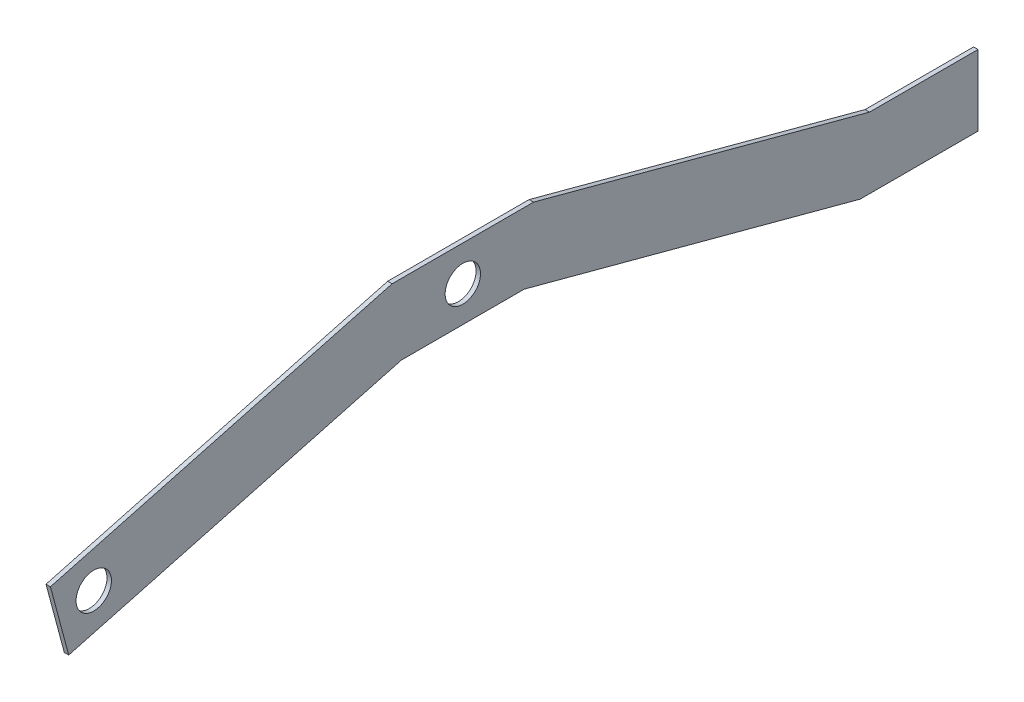
SolidWorks part; units mm, degrees
material "6063-O"
ref_plane "Front" through (0, 0, 0) normal (0, 0, 1) x (1, 0, 0)
ref_plane "Top" through (0, 0, 0) normal (0, 1, 0) x (1, 0, 0)
ref_plane "Right" through (0, 0, 0) normal (1, 0, 0) x (0, 0, -1)
sketch "Sketch1" plane through (0, 0, 0) normal (1, 0, 0) x (0, 0, -1)
  line L0 (-50.8, 25.4) -> (50.8, 25.4)
  line L3 (319.1634, -99.0998) -> (44.1121, -25.4)
  line L4 (44.1121, -25.4) -> (-44.1121, -25.4)
  line L5 (-44.1121, -25.4) -> (-282.9972, -89.4091)
  line L6 (-282.9972, -89.4091) -> (-296.1452, -40.34)
  line L7 (-296.1452, -40.34) -> (-50.8, 25.4)
  line L8 (0, 25.4) -> (0, -25.4) construction
  line L9 (-310.7646, -70.5533) -> (-48606.9507, -13011.4774) construction
  line L13 (601.9041, -58.3005) -> (-49398.0959, -58.3005) construction
  line L14 (-147.7421, -347.18) -> (49852.2579, -347.18) construction
  line L15 (369.9634, -60.1196) -> (369.9634, -337.7005)
  line L16 (369.9634, -337.7005) -> (319.1634, -337.7005)
  line L17 (319.1634, -337.7005) -> (319.1634, -99.0998)
  line L19 (50.8, 25.4) -> (369.9634, -60.1196)
  circle A0 centre (-265.0366, -58.3005) radius 12.7
  circle A1 centre (0, 0) radius 12.7
  point P10 (0, 0)
  point P16 (-289.5712, -64.8746)
  point P24 (344.5634, -337.7005)
  dimension "D8" = 25.4
  dimension "D1" = 50.8
  dimension "D2" = 50.8
  dimension "D3" = 609.6
  dimension "D4" = 279.4
  dimension "D5" = 254
  dimension "D6" = 165
  dimension "D7" = 101.6
  dimension "D9" = 25.4
  dimension "D10" = 50.8
  dimension "D11" = 347.18
  dimension "D13" = 50.8
extrude "Boss-Extrude1" add sketch "Sketch1" along normal blind 3.175
sketch "Sketch3" plane through (3.175, 0, 0) normal (1, 0, 0) x (0, 0, -1)
  line L0 (344.5634, -337.7005) -> (344.5634, -53.3137) construction
  line L1 (319.1634, -337.7005) -> (369.9634, -337.7005) construction
  line L2 (369.9634, -60.1196) -> (50.8, 25.4) construction
  circle A0 centre (344.5634, -312.3005) radius 12.7
  dimension "D1" = 25.4
  dimension "D2" = 25.4
extrude "Cut-Extrude2" cut sketch "Sketch3" against normal through all
sketch "Sketch5" plane through (3.175, 0, 0) normal (1, 0, 0) x (0, 0, -1)
  line L0 (369.9634, -337.7005) -> (369.9634, -60.1196) construction
  line L1 (319.1634, -337.7005) -> (369.9634, -337.7005)
  line L2 (319.1634, -337.7005) -> (319.1634, -90.0505)
  line L3 (319.1634, -90.0505) -> (369.9634, -90.0505)
  line L4 (369.9634, -337.7005) -> (369.9634, -90.0505)
  dimension "D1" = 247.65
extrude "Cut-Extrude4" cut sketch "Sketch5" against normal through all
sketch "Sketch6" plane through (3.175, 0, 0) normal (1, 0, 0) x (0, 0, -1)
  line L1 (369.9634, -90.0505) -> (242.9634, -90.0505)
  line L2 (369.9634, -90.0505) -> (369.9634, -115.4505)
  line L3 (369.9634, -115.4505) -> (242.9634, -115.4505)
  line L4 (242.9634, -90.0505) -> (242.9634, -115.4505)
  dimension "D1" = 25.4
  dimension "D2" = 127
extrude "Cut-Extrude5" cut sketch "Sketch6" against normal through all
sketch "Sketch7" plane through (3.175, 0, 0) normal (1, 0, 0) x (0, 0, -1)
  line L0 (292.0791, -39.2505) -> (369.9634, -39.2505)
  line L1 (369.9634, -60.1196) -> (50.8, 25.4) construction
  line L2 (369.9634, -39.2505) -> (369.9634, -60.1196)
  line L3 (369.9634, -90.0505) -> (285.3912, -90.0505) construction
  line L4 (292.0791, -39.2505) -> (369.9634, -60.1196)
  dimension "D1" = 50.8
extrude "Boss-Extrude2" add sketch "Sketch7" against normal blind 3.175
